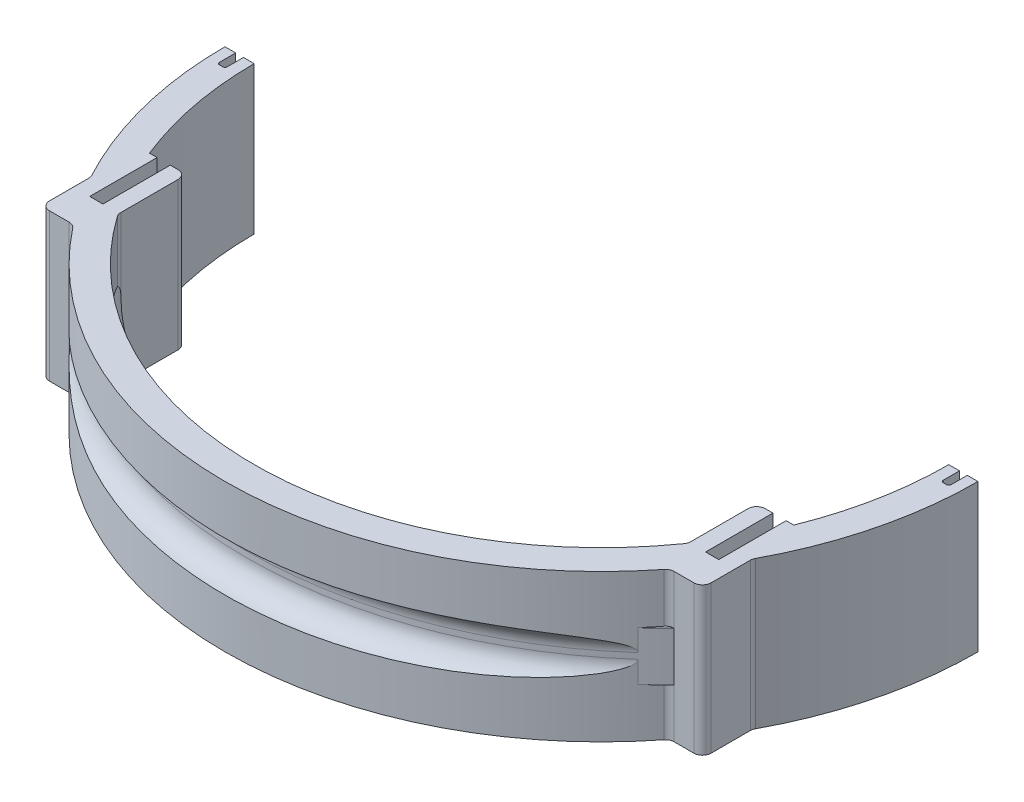
SolidWorks part; units mm, degrees
ref_plane "Front Plane" through (0, 0, 0) normal (0, 0, 1) x (1, 0, 0)
ref_plane "Top Plane" through (0, 0, 0) normal (0, 1, 0) x (1, 0, 0)
ref_plane "Right Plane" through (0, 0, 0) normal (1, 0, 0) x (0, 0, -1)
sketch "Construction Sketch" plane through (0, 0, 0) normal (0, 1, 0) x (1, 0, 0)
  line L0 (-39.5715, 0) -> (39.5715, 0) construction
  line L1 (0, -30.25) -> (0, 30.25) construction
  line L2 (34.71, 22.7218) -> (34.71, 7.2)
  line L3 (-36.21, 22.7218) -> (-34.71, 22.7218)
  line L4 (-36.21, 22.7218) -> (-36.21, 7.2)
  line L5 (-36.21, 7.2) -> (-34.71, 7.2)
  line L6 (-34.71, 22.7218) -> (-34.71, 7.2)
  line L7 (36.21, 7.2) -> (34.71, 7.2)
  line L8 (36.21, 22.7218) -> (36.21, 7.2)
  line L9 (36.21, 22.7218) -> (34.71, 22.7218)
  line L10 (36.21, -22.7218) -> (34.71, -22.7218)
  line L11 (36.21, -22.7218) -> (36.21, -7.2)
  line L12 (36.21, -7.2) -> (34.71, -7.2)
  line L13 (-34.71, -22.7218) -> (-34.71, -7.2)
  line L14 (-36.21, -7.2) -> (-34.71, -7.2)
  line L15 (-36.21, -22.7218) -> (-36.21, -7.2)
  line L16 (-36.21, -22.7218) -> (-34.71, -22.7218)
  line L17 (34.71, -22.7218) -> (34.71, -7.2)
  line L18 (-27.6094, 14.9609) -> (-42.4545, 14.9609) construction
  line L19 (27.6094, 14.9609) -> (42.4545, 14.9609) construction
  line L20 (27.6094, -14.9609) -> (42.4545, -14.9609) construction
  line L21 (-27.6094, -14.9609) -> (-42.4545, -14.9609) construction
  circle A1 centre (0, 0) radius 42.8625
  point P4 (0, 0)
  point P8 (0, 0)
  dimension "D5" = 7.7609
  dimension "D1" = 1.5
  dimension "D2" = 15.5218
  dimension "D3" = 7.2
  dimension "D4" = 34.71
sketch "Sketch3" plane through (0, 0, 0) normal (0, 1, 0) x (1, 0, 0)
  line L0 (-45.7552, 0) -> (45.7552, 0) construction
  line L1 (0, -18.4364) -> (0, 18.4364) construction
  line L2 (34.71, 22.7218) -> (34.71, 14.9609)
  line L3 (-36.23, 22.7218) -> (-34.71, 22.7218)
  line L4 (-36.23, 22.7218) -> (-36.23, 14.9609)
  line L6 (-34.71, 22.7218) -> (-34.71, 14.9609)
  line L8 (36.23, 22.7218) -> (36.23, 14.9609)
  line L9 (36.23, 22.7218) -> (34.71, 22.7218)
  line L10 (36.23, -22.7218) -> (34.71, -22.7218)
  line L11 (36.23, -22.7218) -> (36.23, -14.9609)
  line L13 (-34.71, -22.7218) -> (-34.71, -14.9609)
  line L15 (-36.23, -22.7218) -> (-36.23, -14.9609)
  line L16 (-36.23, -22.7218) -> (-34.71, -22.7218)
  line L17 (34.71, -22.7218) -> (34.71, -14.9609)
  line L18 (-34.8431, 26.4718) -> (-37.105, 26.4718)
  line L19 (-36.23, -14.9609) -> (-37.1022, -14.9609)
  line L21 (36.23, -14.9609) -> (37.1022, -14.9609)
  line L26 (-32.8325, 22.5407) -> (-32.8325, 15.9609)
  line L27 (-42.8625, 33.6264) -> (-42.8625, -34.8883) construction
  line L28 (-33.8325, 14.9609) -> (-34.71, 14.9609)
  line L29 (36.23, 14.9609) -> (37.1022, 14.9609)
  line L31 (-38.105, 25.4718) -> (-38.105, 20.9652)
  line L32 (38.105, 25.4718) -> (38.105, 20.9652)
  line L33 (34.8431, 26.4718) -> (37.105, 26.4718)
  line L34 (33.8325, 14.9609) -> (34.71, 14.9609)
  line L35 (32.8325, 22.5407) -> (32.8325, 15.9609)
  line L36 (38.105, -25.4718) -> (38.105, -20.9652)
  line L37 (34.8431, -26.4718) -> (37.105, -26.4718)
  line L38 (32.8325, -22.5407) -> (32.8325, -15.9609)
  line L39 (33.8325, -14.9609) -> (34.71, -14.9609)
  line L40 (-34.8431, -26.4718) -> (-37.105, -26.4718)
  line L41 (-38.105, -25.4718) -> (-38.105, -20.9652)
  line L42 (-32.8325, -22.5407) -> (-32.8325, -15.9609)
  line L43 (-33.8325, -14.9609) -> (-34.71, -14.9609)
  line L44 (-36.23, 14.9609) -> (-37.1022, 14.9609)
  arc A0 (30.6125, -30.0011) -> (42.8625, 0) centre (0, 0) ccw construction
  arc A1 (-38.2237, 20.4927) -> (-38.2237, -20.4927) centre (0, 0) ccw
  arc A2 (-37.1022, 14.9609) -> (-37.1022, -14.9609) centre (0, 0) ccw
  arc A3 (32.6486, 23.1186) -> (-32.6486, 23.1186) centre (0, 0) ccw
  arc A4 (34.0578, 26.8526) -> (-34.0578, 26.8526) centre (0, 0) ccw
  arc A5 (-32.6486, -23.1186) -> (32.6486, -23.1186) centre (0, 0) ccw
  arc A6 (-34.0578, -26.8526) -> (34.0578, -26.8526) centre (0, 0) ccw
  arc A7 (37.1022, -14.9609) -> (37.1022, 14.9609) centre (0, 0) ccw
  arc A8 (38.2237, -20.4927) -> (38.2237, 20.4927) centre (0, 0) ccw
  arc A9 (-38.105, 20.9652) -> (-38.2237, 20.4927) centre (-39.105, 20.9652) cw
  arc A10 (-34.8431, 26.4718) -> (-34.0578, 26.8526) centre (-34.8431, 27.4718) ccw
  arc A11 (-37.105, 26.4718) -> (-38.105, 25.4718) centre (-37.105, 25.4718) ccw
  arc A12 (-33.8325, 14.9609) -> (-32.8325, 15.9609) centre (-33.8325, 15.9609) ccw
  arc A13 (38.105, 20.9652) -> (38.2237, 20.4927) centre (39.105, 20.9652) ccw
  arc A14 (34.8431, 26.4718) -> (34.0578, 26.8526) centre (34.8431, 27.4718) cw
  arc A15 (-32.6486, -23.1186) -> (-32.8325, -22.5407) centre (-31.8325, -22.5407) cw
  arc A16 (-32.8325, -15.9609) -> (-33.8325, -14.9609) centre (-33.8325, -15.9609) ccw
  arc A17 (-38.105, -20.9652) -> (-38.2237, -20.4927) centre (-39.105, -20.9652) ccw
  arc A18 (-37.105, -26.4718) -> (-38.105, -25.4718) centre (-37.105, -25.4718) cw
  arc A19 (-34.8431, -26.4718) -> (-34.0578, -26.8526) centre (-34.8431, -27.4718) cw
  arc A20 (38.105, -20.9652) -> (38.2237, -20.4927) centre (39.105, -20.9652) cw
  arc A21 (34.8431, -26.4718) -> (34.0578, -26.8526) centre (34.8431, -27.4718) ccw
  arc A22 (32.6486, -23.1186) -> (32.8325, -22.5407) centre (31.8325, -22.5407) ccw
  arc A23 (-32.8325, 22.5407) -> (-32.6486, 23.1186) centre (-31.8325, 22.5407) cw
  arc A24 (38.105, -25.4718) -> (37.105, -26.4718) centre (37.105, -25.4718) cw
  arc A25 (32.8325, -15.9609) -> (33.8325, -14.9609) centre (33.8325, -15.9609) cw
  arc A26 (32.8325, 22.5407) -> (32.6486, 23.1186) centre (31.8325, 22.5407) ccw
  arc A27 (33.8325, 14.9609) -> (32.8325, 15.9609) centre (33.8325, 15.9609) cw
  arc A28 (38.105, 25.4718) -> (37.105, 26.4718) centre (37.105, 25.4718) ccw
  point P3 (0, 0)
  point P6 (0, 0)
  point P54 (-38.105, 20.7125)
  point P57 (-34.3547, 26.4718)
  point P60 (-38.105, 26.4718)
  point P63 (-32.8325, 14.9609)
  point P66 (38.105, 20.7125)
  point P69 (34.3547, 26.4718)
  point P74 (-32.8325, -14.9609)
  point P77 (-38.105, -20.7125)
  point P80 (-38.105, -26.4718)
  point P83 (-34.3547, -26.4718)
  point P86 (38.105, -20.7125)
  point P89 (34.3547, -26.4718)
  point P96 (38.105, -26.4718)
  point P99 (32.8325, -14.9609)
  point P102 (32.8325, 22.8567)
  point P105 (32.8325, 14.9609)
  point P108 (38.105, 26.4718)
  dimension "D3" = 80.01
  dimension "D6" = 7.7609
  dimension "D5" = 86.741
  dimension "D10" = 1
  dimension "D11" = 1
  dimension "D1" = 1.52
  dimension "D2" = 10.03
  dimension "D4" = 34.71
  dimension "D7" = 3.75
  dimension "D8" = 1.875
  dimension "D9" = 8.1525
extrude "Boss-Extrude1" add sketch "Sketch3" along normal blind 5.6667 contours L36 A8 L32 L33 A4 L18 L31 A1 L27 L41 L40 A6 L37 A7 L21 L11 L10 L17 L39 L38 A5 L42 L43 L13 L16 L15 L19 A2 L44 L4 L3 L6 L28 L26 A3 L35 L34 L2 L9 L8 L29
sketch "Sketch4" plane through (0, 5.6667, 0) normal (0, 1, 0) x (1, 0, 0)
  line L0 (-32.8325, 22.5407) -> (-32.8325, 15.9609) construction
  line L1 (-34.71, 22.7218) -> (-34.71, 14.9609) construction
  line L2 (-33.8325, 14.9609) -> (-34.71, 14.9609) construction
  line L3 (-36.23, 22.7218) -> (-34.71, 22.7218) construction
  line L4 (-36.23, 22.7218) -> (-36.23, 14.9609) construction
  line L5 (-36.23, 14.9609) -> (-37.1022, 14.9609) construction
  line L6 (-36.23, -22.7218) -> (-36.23, -14.9609) construction
  line L7 (-36.23, -14.9609) -> (-37.1022, -14.9609) construction
  line L8 (38.105, 20.9652) -> (38.105, 25.4718)
  line L9 (37.105, 26.4718) -> (34.8431, 26.4718)
  line L10 (-34.8431, 26.4718) -> (-37.105, 26.4718)
  line L11 (-38.105, 25.4718) -> (-38.105, 20.9652)
  line L12 (-38.105, -20.9652) -> (-38.105, -25.4718)
  line L13 (-37.105, -26.4718) -> (-34.8431, -26.4718)
  line L14 (34.8431, -26.4718) -> (37.105, -26.4718)
  line L15 (38.105, -25.4718) -> (38.105, -20.9652)
  line L16 (38.105, 20.9652) -> (38.105, 25.4718)
  line L17 (37.105, 26.4718) -> (34.8431, 26.4718)
  line L18 (-34.8431, 26.4718) -> (-37.105, 26.4718)
  line L19 (-38.105, 25.4718) -> (-38.105, 20.9652)
  line L20 (-38.105, -20.9652) -> (-38.105, -25.4718)
  line L21 (-37.105, -26.4718) -> (-34.8431, -26.4718)
  line L22 (34.8431, -26.4718) -> (37.105, -26.4718)
  line L23 (38.105, -25.4718) -> (38.105, -20.9652)
  line L24 (-33.8325, -14.9609) -> (-34.71, -14.9609) construction
  line L25 (-34.71, -22.7218) -> (-34.71, -14.9609) construction
  line L26 (-32.8325, -22.5407) -> (-32.8325, -15.9609) construction
  line L27 (-36.23, -22.7218) -> (-34.71, -22.7218) construction
  line L28 (32.8325, -22.5407) -> (32.8325, -15.9609) construction
  line L29 (34.71, -22.7218) -> (34.71, -14.9609) construction
  line L30 (36.23, -22.7218) -> (34.71, -22.7218) construction
  line L31 (36.23, -22.7218) -> (36.23, -14.9609) construction
  line L32 (33.8325, -14.9609) -> (34.71, -14.9609) construction
  line L33 (36.23, -14.9609) -> (37.1022, -14.9609) construction
  line L34 (36.23, 22.7218) -> (34.71, 22.7218) construction
  line L35 (36.23, 22.7218) -> (36.23, 14.9609) construction
  line L36 (34.71, 22.7218) -> (34.71, 14.9609) construction
  line L37 (32.8325, 22.5407) -> (32.8325, 15.9609) construction
  line L38 (33.8325, 14.9609) -> (34.71, 14.9609) construction
  line L39 (36.23, 14.9609) -> (37.1022, 14.9609) construction
  line L40 (36.23, 14.9609) -> (37.1022, 14.9609)
  line L41 (33.8325, 14.9609) -> (34.71, 14.9609)
  line L42 (32.8325, 22.5407) -> (32.8325, 15.9609)
  line L43 (34.71, 22.7218) -> (34.71, 14.9609)
  line L44 (36.23, 22.7218) -> (36.23, 14.9609)
  line L45 (36.23, 22.7218) -> (34.71, 22.7218)
  line L46 (36.23, -14.9609) -> (37.1022, -14.9609)
  line L47 (33.8325, -14.9609) -> (34.71, -14.9609)
  line L48 (36.23, -22.7218) -> (36.23, -14.9609)
  line L49 (36.23, -22.7218) -> (34.71, -22.7218)
  line L50 (34.71, -22.7218) -> (34.71, -14.9609)
  line L51 (32.8325, -22.5407) -> (32.8325, -15.9609)
  line L52 (-36.23, -22.7218) -> (-34.71, -22.7218)
  line L53 (-32.8325, -22.5407) -> (-32.8325, -15.9609)
  line L54 (-34.71, -22.7218) -> (-34.71, -14.9609)
  line L55 (-33.8325, -14.9609) -> (-34.71, -14.9609)
  line L56 (-36.23, -14.9609) -> (-37.1022, -14.9609)
  line L57 (-36.23, -22.7218) -> (-36.23, -14.9609)
  line L58 (-36.23, 14.9609) -> (-37.1022, 14.9609)
  line L59 (-36.23, 22.7218) -> (-36.23, 14.9609)
  line L60 (-36.23, 22.7218) -> (-34.71, 22.7218)
  line L61 (-33.8325, 14.9609) -> (-34.71, 14.9609)
  line L62 (-34.71, 22.7218) -> (-34.71, 14.9609)
  line L63 (-32.8325, 22.5407) -> (-32.8325, 15.9609)
  arc A1 (32.6486, 23.1186) -> (-32.6486, 23.1186) centre (0, 0) ccw construction
  arc A2 (-32.6486, 23.1186) -> (-32.8325, 22.5407) centre (-31.8325, 22.5407) ccw construction
  arc A3 (-33.8325, 14.9609) -> (-32.8325, 15.9609) centre (-33.8325, 15.9609) ccw construction
  arc A13 (32.8325, 22.5407) -> (32.6486, 23.1186) centre (31.8325, 22.5407) ccw
  arc A14 (32.8325, 15.9609) -> (33.8325, 14.9609) centre (33.8325, 15.9609) ccw
  arc A15 (37.1022, -14.9609) -> (37.1022, 14.9609) centre (0, 0) ccw
  arc A16 (38.105, 25.4718) -> (37.105, 26.4718) centre (37.105, 25.4718) ccw
  arc A17 (34.0578, 26.8526) -> (34.8431, 26.4718) centre (34.8431, 27.4718) ccw
  arc A18 (34.0578, 26.8526) -> (-34.0578, 26.8526) centre (0, 0) ccw
  arc A19 (-34.8431, 26.4718) -> (-34.0578, 26.8526) centre (-34.8431, 27.4718) ccw
  arc A20 (-37.105, 26.4718) -> (-38.105, 25.4718) centre (-37.105, 25.4718) ccw
  arc A21 (-38.2237, 20.4927) -> (-38.105, 20.9652) centre (-39.105, 20.9652) ccw
  arc A22 (-38.2237, 20.4927) -> (-38.2237, -20.4927) centre (0, 0) ccw
  arc A23 (-38.105, -20.9652) -> (-38.2237, -20.4927) centre (-39.105, -20.9652) ccw
  arc A24 (-38.105, -25.4718) -> (-37.105, -26.4718) centre (-37.105, -25.4718) ccw
  arc A25 (-34.0578, -26.8526) -> (-34.8431, -26.4718) centre (-34.8431, -27.4718) ccw
  arc A26 (-34.0578, -26.8526) -> (34.0578, -26.8526) centre (0, 0) ccw
  arc A27 (34.8431, -26.4718) -> (34.0578, -26.8526) centre (34.8431, -27.4718) ccw
  arc A28 (37.105, -26.4718) -> (38.105, -25.4718) centre (37.105, -25.4718) ccw
  arc A29 (38.2237, -20.4927) -> (38.105, -20.9652) centre (39.105, -20.9652) ccw
  arc A30 (38.2237, -20.4927) -> (38.2237, 20.4927) centre (0, 0) ccw
  arc A31 (38.105, 20.9652) -> (38.2237, 20.4927) centre (39.105, 20.9652) ccw
  arc A32 (38.105, 25.4718) -> (37.105, 26.4718) centre (37.105, 25.4718) ccw
  arc A33 (34.0578, 26.8526) -> (34.8431, 26.4718) centre (34.8431, 27.4718) ccw
  arc A34 (34.0578, 26.8526) -> (-34.0578, 26.8526) centre (0, 0) ccw
  arc A35 (-34.8431, 26.4718) -> (-34.0578, 26.8526) centre (-34.8431, 27.4718) ccw
  arc A36 (-37.105, 26.4718) -> (-38.105, 25.4718) centre (-37.105, 25.4718) ccw
  arc A37 (-38.2237, 20.4927) -> (-38.105, 20.9652) centre (-39.105, 20.9652) ccw
  arc A38 (-38.2237, 20.4927) -> (-38.2237, -20.4927) centre (0, 0) ccw
  arc A39 (-38.105, -20.9652) -> (-38.2237, -20.4927) centre (-39.105, -20.9652) ccw
  arc A40 (-38.105, -25.4718) -> (-37.105, -26.4718) centre (-37.105, -25.4718) ccw
  arc A41 (-34.0578, -26.8526) -> (-34.8431, -26.4718) centre (-34.8431, -27.4718) ccw
  arc A42 (-34.0578, -26.8526) -> (34.0578, -26.8526) centre (0, 0) ccw
  arc A43 (34.8431, -26.4718) -> (34.0578, -26.8526) centre (34.8431, -27.4718) ccw
  arc A44 (37.105, -26.4718) -> (38.105, -25.4718) centre (37.105, -25.4718) ccw
  arc A45 (38.2237, -20.4927) -> (38.105, -20.9652) centre (39.105, -20.9652) ccw
  arc A46 (38.2237, -20.4927) -> (38.2237, 20.4927) centre (0, 0) ccw
  arc A47 (38.105, 20.9652) -> (38.2237, 20.4927) centre (39.105, 20.9652) ccw
  arc A48 (33.8325, -14.9609) -> (32.8325, -15.9609) centre (33.8325, -15.9609) ccw
  arc A49 (32.6486, -23.1186) -> (32.8325, -22.5407) centre (31.8325, -22.5407) ccw
  arc A50 (-32.6486, -23.1186) -> (32.6486, -23.1186) centre (0, 0) ccw
  arc A51 (-32.8325, -22.5407) -> (-32.6486, -23.1186) centre (-31.8325, -22.5407) ccw
  arc A52 (-32.8325, -15.9609) -> (-33.8325, -14.9609) centre (-33.8325, -15.9609) ccw
  arc A53 (-37.1022, 14.9609) -> (-37.1022, -14.9609) centre (0, 0) ccw
  arc A54 (-33.8325, 14.9609) -> (-32.8325, 15.9609) centre (-33.8325, 15.9609) ccw
  arc A55 (-32.6486, 23.1186) -> (-32.8325, 22.5407) centre (-31.8325, 22.5407) ccw
  arc A56 (32.6486, 23.1186) -> (-32.6486, 23.1186) centre (0, 0) ccw
  dimension "D1" = 0
ref_plane "Plane1" through (0, 11.3333, 0) normal (0, 1, 0) x (1, 0, 0)
sketch "Sketch5" plane through (0, 11.3333, 0) normal (0, 1, 0) x (1, 0, 0)
  line L0 (38.105, 20.9652) -> (38.105, 25.4718)
  line L1 (37.105, 26.4718) -> (34.8431, 26.4718)
  line L2 (-34.8431, 26.4718) -> (-37.105, 26.4718)
  line L3 (-38.105, 25.4718) -> (-38.105, 20.9652)
  line L4 (-38.105, -20.9652) -> (-38.105, -25.4718)
  line L5 (-37.105, -26.4718) -> (-34.8431, -26.4718)
  line L6 (34.8431, -26.4718) -> (37.105, -26.4718)
  line L7 (38.105, -25.4718) -> (38.105, -20.9652)
  line L8 (36.23, 14.9609) -> (37.1022, 14.9609)
  line L9 (33.8325, 14.9609) -> (34.71, 14.9609)
  line L10 (32.8325, 22.5407) -> (32.8325, 15.9609)
  line L11 (34.71, 22.7218) -> (34.71, 14.9609)
  line L12 (36.23, 22.7218) -> (36.23, 14.9609)
  line L13 (36.23, 22.7218) -> (34.71, 22.7218)
  line L14 (36.23, -14.9609) -> (37.1022, -14.9609)
  line L15 (33.8325, -14.9609) -> (34.71, -14.9609)
  line L16 (36.23, -22.7218) -> (36.23, -14.9609)
  line L17 (36.23, -22.7218) -> (34.71, -22.7218)
  line L18 (34.71, -22.7218) -> (34.71, -14.9609)
  line L19 (32.8325, -22.5407) -> (32.8325, -15.9609)
  line L20 (-36.23, -22.7218) -> (-34.71, -22.7218)
  line L21 (-32.8325, -22.5407) -> (-32.8325, -15.9609)
  line L22 (-34.71, -22.7218) -> (-34.71, -14.9609)
  line L23 (-33.8325, -14.9609) -> (-34.71, -14.9609)
  line L24 (-36.23, -14.9609) -> (-37.1022, -14.9609)
  line L25 (-36.23, -22.7218) -> (-36.23, -14.9609)
  line L26 (-36.23, 14.9609) -> (-37.1022, 14.9609)
  line L27 (-36.23, 22.7218) -> (-36.23, 14.9609)
  line L28 (-36.23, 22.7218) -> (-34.71, 22.7218)
  line L29 (-33.8325, 14.9609) -> (-34.71, 14.9609)
  line L30 (-34.71, 22.7218) -> (-34.71, 14.9609)
  line L31 (-32.8325, 22.5407) -> (-32.8325, 15.9609)
  line L32 (-76.2008, 0) -> (76.2008, 0) construction
  arc A1 (32.8325, 15.9609) -> (33.8325, 14.9609) centre (33.8325, 15.9609) ccw
  arc A2 (37.1022, -14.9609) -> (37.1022, 14.9609) centre (0, 0) ccw
  arc A3 (38.105, 25.4718) -> (37.105, 26.4718) centre (37.105, 25.4718) ccw
  arc A7 (-37.105, 26.4718) -> (-38.105, 25.4718) centre (-37.105, 25.4718) ccw
  arc A8 (-38.2237, 20.4927) -> (-38.105, 20.9652) centre (-39.105, 20.9652) ccw
  arc A9 (-38.2237, 20.4927) -> (-38.2237, -20.4927) centre (0, 0) ccw
  arc A10 (-38.105, -20.9652) -> (-38.2237, -20.4927) centre (-39.105, -20.9652) ccw
  arc A11 (-38.105, -25.4718) -> (-37.105, -26.4718) centre (-37.105, -25.4718) ccw
  arc A15 (37.105, -26.4718) -> (38.105, -25.4718) centre (37.105, -25.4718) ccw
  arc A16 (38.2237, -20.4927) -> (38.105, -20.9652) centre (39.105, -20.9652) ccw
  arc A17 (38.2237, -20.4927) -> (38.2237, 20.4927) centre (0, 0) ccw
  arc A18 (38.105, 20.9652) -> (38.2237, 20.4927) centre (39.105, 20.9652) ccw
  arc A19 (33.8325, -14.9609) -> (32.8325, -15.9609) centre (33.8325, -15.9609) ccw
  arc A23 (-32.8325, -15.9609) -> (-33.8325, -14.9609) centre (-33.8325, -15.9609) ccw
  arc A24 (-37.1022, 14.9609) -> (-37.1022, -14.9609) centre (0, 0) ccw
  arc A25 (-33.8325, 14.9609) -> (-32.8325, 15.9609) centre (-33.8325, 15.9609) ccw
  arc A28 (-32.8325, 22.5407) -> (32.8325, 22.5407) centre (0, -10.2918) cw
  arc A29 (-32.8325, -22.5407) -> (32.8325, -22.5407) centre (0, 10.2918) ccw
  arc A30 (-34.8431, 26.4718) -> (34.8431, 26.4718) centre (0, -8.3713) cw
  arc A31 (-34.8431, -26.4718) -> (34.8431, -26.4718) centre (0, 8.3713) ccw
  point P87 (0, 0)
extrude "Boss-Extrude3" add sketch "Sketch5" against normal blind 5.6667
sketch "Sketch7" plane through (0, 11.3333, 0) normal (0, 1, 0) x (1, 0, 0)
  line L0 (38.105, 20.9652) -> (38.105, 25.4718)
  line L1 (37.105, 26.4718) -> (34.8431, 26.4718)
  line L2 (-34.8431, 26.4718) -> (-37.105, 26.4718)
  line L3 (-38.105, 25.4718) -> (-38.105, 20.9652)
  line L4 (-38.105, -20.9652) -> (-38.105, -25.4718)
  line L5 (-37.105, -26.4718) -> (-34.8431, -26.4718)
  line L6 (34.8431, -26.4718) -> (37.105, -26.4718)
  line L7 (38.105, -25.4718) -> (38.105, -20.9652)
  line L8 (36.23, 14.9609) -> (37.1022, 14.9609)
  line L9 (33.8325, 14.9609) -> (34.71, 14.9609)
  line L10 (32.8325, 22.5407) -> (32.8325, 15.9609)
  line L11 (34.71, 22.7218) -> (34.71, 14.9609)
  line L12 (36.23, 22.7218) -> (36.23, 14.9609)
  line L13 (36.23, 22.7218) -> (34.71, 22.7218)
  line L14 (36.23, -14.9609) -> (37.1022, -14.9609)
  line L15 (33.8325, -14.9609) -> (34.71, -14.9609)
  line L16 (36.23, -22.7218) -> (36.23, -14.9609)
  line L17 (36.23, -22.7218) -> (34.71, -22.7218)
  line L18 (34.71, -22.7218) -> (34.71, -14.9609)
  line L19 (32.8325, -22.5407) -> (32.8325, -15.9609)
  line L20 (-36.23, -22.7218) -> (-34.71, -22.7218)
  line L21 (-32.8325, -22.5407) -> (-32.8325, -15.9609)
  line L22 (-34.71, -22.7218) -> (-34.71, -14.9609)
  line L23 (-33.8325, -14.9609) -> (-34.71, -14.9609)
  line L24 (-36.23, -14.9609) -> (-37.1022, -14.9609)
  line L25 (-36.23, -22.7218) -> (-36.23, -14.9609)
  line L26 (-36.23, 14.9609) -> (-37.1022, 14.9609)
  line L27 (-36.23, 22.7218) -> (-36.23, 14.9609)
  line L28 (-36.23, 22.7218) -> (-34.71, 22.7218)
  line L29 (-33.8325, 14.9609) -> (-34.71, 14.9609)
  line L30 (-34.71, 22.7218) -> (-34.71, 14.9609)
  line L31 (-32.8325, 22.5407) -> (-32.8325, 15.9609)
  arc A0 (32.8325, 22.5407) -> (32.6486, 23.1186) centre (31.8325, 22.5407) ccw
  arc A1 (32.8325, 15.9609) -> (33.8325, 14.9609) centre (33.8325, 15.9609) ccw
  arc A2 (37.1022, -14.9609) -> (37.1022, 14.9609) centre (0, 0) ccw
  arc A3 (38.105, 25.4718) -> (37.105, 26.4718) centre (37.105, 25.4718) ccw
  arc A4 (34.0578, 26.8526) -> (34.8431, 26.4718) centre (34.8431, 27.4718) ccw
  arc A5 (34.0578, 26.8526) -> (-34.0578, 26.8526) centre (0, 0) ccw
  arc A6 (-34.8431, 26.4718) -> (-34.0578, 26.8526) centre (-34.8431, 27.4718) ccw
  arc A7 (-37.105, 26.4718) -> (-38.105, 25.4718) centre (-37.105, 25.4718) ccw
  arc A8 (-38.2237, 20.4927) -> (-38.105, 20.9652) centre (-39.105, 20.9652) ccw
  arc A9 (-38.2237, 20.4927) -> (-38.2237, -20.4927) centre (0, 0) ccw
  arc A10 (-38.105, -20.9652) -> (-38.2237, -20.4927) centre (-39.105, -20.9652) ccw
  arc A11 (-38.105, -25.4718) -> (-37.105, -26.4718) centre (-37.105, -25.4718) ccw
  arc A12 (-34.0578, -26.8526) -> (-34.8431, -26.4718) centre (-34.8431, -27.4718) ccw
  arc A13 (-34.0578, -26.8526) -> (34.0578, -26.8526) centre (0, 0) ccw
  arc A14 (34.8431, -26.4718) -> (34.0578, -26.8526) centre (34.8431, -27.4718) ccw
  arc A15 (37.105, -26.4718) -> (38.105, -25.4718) centre (37.105, -25.4718) ccw
  arc A16 (38.2237, -20.4927) -> (38.105, -20.9652) centre (39.105, -20.9652) ccw
  arc A17 (38.2237, -20.4927) -> (38.2237, 20.4927) centre (0, 0) ccw
  arc A18 (38.105, 20.9652) -> (38.2237, 20.4927) centre (39.105, 20.9652) ccw
  arc A19 (33.8325, -14.9609) -> (32.8325, -15.9609) centre (33.8325, -15.9609) ccw
  arc A20 (32.6486, -23.1186) -> (32.8325, -22.5407) centre (31.8325, -22.5407) ccw
  arc A21 (-32.6486, -23.1186) -> (32.6486, -23.1186) centre (0, 0) ccw
  arc A22 (-32.8325, -22.5407) -> (-32.6486, -23.1186) centre (-31.8325, -22.5407) ccw
  arc A23 (-32.8325, -15.9609) -> (-33.8325, -14.9609) centre (-33.8325, -15.9609) ccw
  arc A24 (-37.1022, 14.9609) -> (-37.1022, -14.9609) centre (0, 0) ccw
  arc A25 (-33.8325, 14.9609) -> (-32.8325, 15.9609) centre (-33.8325, 15.9609) ccw
  arc A26 (-32.6486, 23.1186) -> (-32.8325, 22.5407) centre (-31.8325, 22.5407) ccw
  arc A27 (32.6486, 23.1186) -> (-32.6486, 23.1186) centre (0, 0) ccw
extrude "Boss-Extrude4" add sketch "Sketch7" along normal blind 5.6667
fillet "Fillet1" radius 2.5 8 edges at (0, 5.6667, -40.9043) (0, 11.3333, -40.9043) (0, 5.6667, -36.1403) (0, 11.3333, -36.1403) (0, 5.6667, 40.9043) (0, 11.3333, 40.9043) (0, 5.6667, 36.1403) (0, 11.3333, 36.1403)
sketch "Sketch8" plane through (0, 17, 0) normal (0, 1, 0) x (1, 0, 0)
  line L0 (-63.4296, 0) -> (-42.1378, 0) construction
  line L8 (38.105, 20.9652) -> (38.105, 25.4718)
  line L9 (37.105, 26.4718) -> (34.8431, 26.4718)
  line L10 (-34.8431, 26.4718) -> (-37.105, 26.4718)
  line L11 (-38.105, 25.4718) -> (-38.105, 20.9652)
  line L12 (-38.105, -20.9652) -> (-38.105, -25.4718)
  line L13 (-37.105, -26.4718) -> (-34.8431, -26.4718)
  line L14 (34.8431, -26.4718) -> (37.105, -26.4718)
  line L15 (38.105, -25.4718) -> (38.105, -20.9652)
  line L16 (38.105, 20.9652) -> (38.105, 25.4718)
  line L17 (37.105, 26.4718) -> (34.8431, 26.4718)
  line L18 (-34.8431, 26.4718) -> (-37.105, 26.4718)
  line L19 (-38.105, 25.4718) -> (-38.105, 20.9652)
  line L25 (36.23, 22.7218) -> (36.23, 14.9609) construction
  line L26 (36.23, 22.7218) -> (34.71, 22.7218) construction
  line L27 (34.71, 22.7218) -> (34.71, 14.9609) construction
  line L28 (32.8325, 22.5407) -> (32.8325, 15.9609) construction
  line L37 (-36.23, 22.7218) -> (-36.23, 14.9609) construction
  line L38 (-36.23, 22.7218) -> (-34.71, 22.7218) construction
  line L39 (-34.71, 22.7218) -> (-34.71, 14.9609) construction
  line L40 (-32.8325, 22.5407) -> (-32.8325, 15.9609) construction
  line L47 (36.23, 14.9609) -> (37.1022, 14.9609)
  line L48 (33.8325, 14.9609) -> (34.71, 14.9609)
  line L49 (36.23, 22.7218) -> (36.23, 14.9609)
  line L50 (36.23, 22.7218) -> (34.71, 22.7218)
  line L51 (34.71, 22.7218) -> (34.71, 14.9609)
  line L52 (32.8325, 22.5407) -> (32.8325, 15.9609)
  line L59 (-36.23, 14.9609) -> (-37.1022, 14.9609)
  line L60 (-33.8325, 14.9609) -> (-34.71, 14.9609)
  line L61 (-36.23, 22.7218) -> (-36.23, 14.9609)
  line L62 (-36.23, 22.7218) -> (-34.71, 22.7218)
  line L63 (-34.71, 22.7218) -> (-34.71, 14.9609)
  line L64 (-32.8325, 22.5407) -> (-32.8325, 15.9609)
  line L65 (43.3705, 0) -> (42.1378, 0)
  line L66 (43.3705, 0) -> (43.3705, 8.215) construction
  line L67 (40.005, 0) -> (40.005, 8.215) construction
  line L68 (0, -51.8966) -> (0, 51.8966) construction
  line L70 (41.2378, 0) -> (41.2378, -2.125)
  line L71 (41.2378, -2.125) -> (42.1378, -2.125)
  line L72 (42.1378, 0) -> (42.1378, -2.125)
  line L73 (41.6878, 0) -> (42.1378, -2.125) construction
  line L74 (-42.1378, 0) -> (-43.3705, 0)
  line L75 (-40.005, 0) -> (-41.2378, 0)
  line L76 (40.005, 0) -> (41.2378, 0) construction
  line L77 (-40.005, 0) -> (-40.005, 8.215) construction
  line L78 (-43.3705, 0) -> (-43.3705, 8.215) construction
  line L79 (-42.1378, 0) -> (-42.1378, -2.125)
  line L80 (-41.2378, -2.125) -> (-42.1378, -2.125)
  line L81 (-41.2378, 0) -> (-41.2378, -2.125)
  line L83 (41.2378, 0) -> (40.005, 0)
  line L84 (42.1378, 0) -> (63.4296, 0) construction
  line L85 (-41.2378, 0) -> (-40.005, 0) construction
  arc A0 (43.3705, 0) -> (-43.3705, 0) centre (0, 0) ccw construction
  arc A4 (32.8325, 15.9609) -> (33.8325, 14.9609) centre (33.8325, 15.9609) ccw construction
  arc A5 (32.8325, 22.5407) -> (32.6486, 23.1186) centre (31.8325, 22.5407) ccw construction
  arc A10 (-33.8325, 14.9609) -> (-32.8325, 15.9609) centre (-33.8325, 15.9609) ccw construction
  arc A11 (-32.6486, 23.1186) -> (-32.8325, 22.5407) centre (-31.8325, 22.5407) ccw construction
  arc A12 (32.6486, 23.1186) -> (-32.6486, 23.1186) centre (0, 0) ccw construction
  arc A15 (40.005, 0) -> (37.1022, 14.9609) centre (0, 0) ccw
  arc A16 (38.105, 20.9652) -> (38.2237, 20.4927) centre (39.105, 20.9652) ccw
  arc A17 (38.105, 25.4718) -> (37.105, 26.4718) centre (37.105, 25.4718) ccw
  arc A18 (34.0578, 26.8526) -> (34.8431, 26.4718) centre (34.8431, 27.4718) ccw
  arc A19 (34.0578, 26.8526) -> (-34.0578, 26.8526) centre (0, 0) ccw
  arc A20 (-34.8431, 26.4718) -> (-34.0578, 26.8526) centre (-34.8431, 27.4718) ccw
  arc A21 (-37.105, 26.4718) -> (-38.105, 25.4718) centre (-37.105, 25.4718) ccw
  arc A22 (-38.2237, 20.4927) -> (-38.105, 20.9652) centre (-39.105, 20.9652) ccw
  arc A23 (-38.2237, 20.4927) -> (-38.2237, -20.4927) centre (0, 0) ccw
  arc A24 (-38.105, -20.9652) -> (-38.2237, -20.4927) centre (-39.105, -20.9652) ccw
  arc A25 (-38.105, -25.4718) -> (-37.105, -26.4718) centre (-37.105, -25.4718) ccw
  arc A26 (-34.0578, -26.8526) -> (-34.8431, -26.4718) centre (-34.8431, -27.4718) ccw
  arc A27 (-34.0578, -26.8526) -> (34.0578, -26.8526) centre (0, 0) ccw
  arc A28 (34.8431, -26.4718) -> (34.0578, -26.8526) centre (34.8431, -27.4718) ccw
  arc A29 (37.105, -26.4718) -> (38.105, -25.4718) centre (37.105, -25.4718) ccw
  arc A30 (38.2237, -20.4927) -> (38.105, -20.9652) centre (39.105, -20.9652) ccw
  arc A31 (38.2237, -20.4927) -> (38.2237, 20.4927) centre (0, 0) ccw
  arc A32 (38.105, 20.9652) -> (38.2237, 20.4927) centre (39.105, 20.9652) ccw
  arc A33 (38.105, 25.4718) -> (37.105, 26.4718) centre (37.105, 25.4718) ccw
  arc A34 (34.0578, 26.8526) -> (34.8431, 26.4718) centre (34.8431, 27.4718) ccw
  arc A35 (34.0578, 26.8526) -> (-34.0578, 26.8526) centre (0, 0) ccw
  arc A36 (-34.8431, 26.4718) -> (-34.0578, 26.8526) centre (-34.8431, 27.4718) ccw
  arc A37 (-37.105, 26.4718) -> (-38.105, 25.4718) centre (-37.105, 25.4718) ccw
  arc A38 (-38.2237, 20.4927) -> (-38.105, 20.9652) centre (-39.105, 20.9652) ccw
  arc A39 (-38.2237, 20.4927) -> (-43.3705, 0) centre (0, 0) ccw
  arc A47 (43.3705, 0) -> (38.2237, 20.4927) centre (0, 0) ccw
  arc A48 (32.8325, 15.9609) -> (33.8325, 14.9609) centre (33.8325, 15.9609) ccw
  arc A49 (32.8325, 22.5407) -> (32.6486, 23.1186) centre (31.8325, 22.5407) ccw
  arc A53 (-37.1022, 14.9609) -> (-40.005, 0) centre (0, 0) ccw
  arc A54 (-33.8325, 14.9609) -> (-32.8325, 15.9609) centre (-33.8325, 15.9609) ccw
  arc A55 (-32.6486, 23.1186) -> (-32.8325, 22.5407) centre (-31.8325, 22.5407) ccw
  arc A56 (32.6486, 23.1186) -> (-32.6486, 23.1186) centre (0, 0) ccw
  point P13 (0, 0)
  point P90 (41.6878, 0)
  point P93 (43.3705, 0)
  point P96 (40.005, 0)
  point P104 (0, 0)
  point P112 (-40.005, 0)
  point P113 (-43.3705, 0)
  point P114 (-41.6878, 0)
  dimension "D2" = 43.3705
  dimension "D3" = 3.3655
  dimension "D7" = 0.9
  dimension "D1" = 0
extrude "Cut-Extrude1" cut sketch "Sketch8" against normal through all
sketch "Sketch9" plane through (0, 17, 0) normal (0, 1, 0) x (1, 0, 0)
  line L1 (-51.2813, 44.0761) -> (50.9456, 44.0761)
  line L2 (-51.2813, 44.0761) -> (-51.2813, 10.3485)
  line L3 (-51.2813, 10.3485) -> (50.9456, 10.3485)
  line L4 (50.9456, 44.0761) -> (50.9456, 10.3485)
extrude "Cut-Extrude2" cut sketch "Sketch9" against normal through all
fillet "Fillet2" radius 0.25 4 edges at (41.2378, 8.5, 2.125) (42.1378, 8.5, 2.125) (-41.2378, 8.5, 2.125) (-42.1378, 8.5, 2.125)
